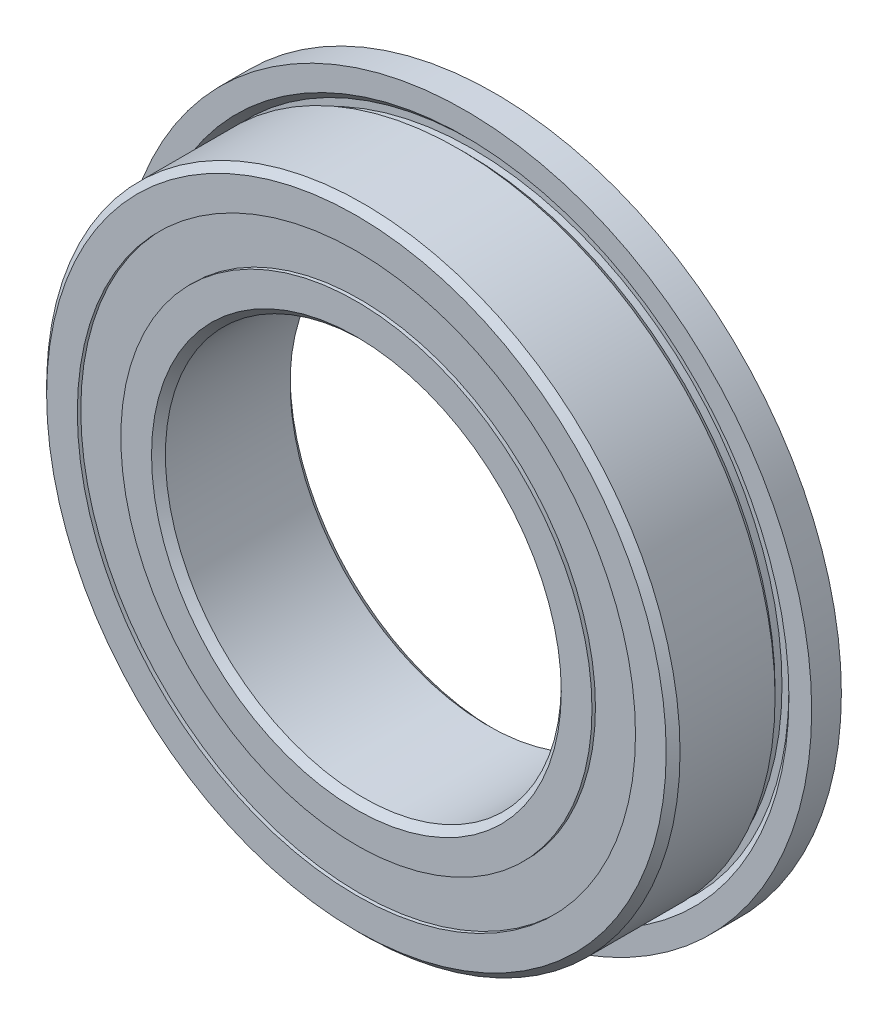
SolidWorks part; units mm, degrees
material "Alloy Steel"
ref_plane "Front Plane" through (0, 0, 0) normal (0, 0, 1) x (1, 0, 0)
ref_plane "Top Plane" through (0, 0, 0) normal (0, 1, 0) x (1, 0, 0)
ref_plane "Right Plane" through (0, 0, 0) normal (1, 0, 0) x (0, 0, -1)
sketch "Sketch1" plane through (0, 0, 0) normal (0, 0, 1) x (1, 0, 0)
  circle A0 centre (0, 0) radius 10
  dimension "ID" = 20
sketch "Sketch2" plane through (0, 0, 0) normal (1, 0, 0) x (0, 0, -1)
  line L0 (-3.5, 0) -> (3.5, 0) construction
  line L1 (0, 16) -> (0, -16) construction
  line L2 (3.15, 16) -> (-3.15, 16) construction
  line L3 (-3.15, 16) -> (-3.5, 15.65)
  line L4 (-3.5, 15.65) -> (-3.5, 14.0989)
  line L5 (-3.5, 14.0989) -> (-1.5556, 14.0989)
  line L6 (3.5, 14.0989) -> (1.5556, 14.0989)
  line L7 (3.5, 15.65) -> (3.5, 14.0989)
  line L8 (3.15, 16) -> (3.5, 15.65) construction
  line L9 (0, 16) -> (0, 13) construction
  line L10 (0, 13) -> (0, 10) construction
  line L11 (2, 0) -> (2, 16) construction
  line L12 (3.5, 15.65) -> (3.5, 17.5)
  line L13 (3.5, 17.5) -> (2, 17.5)
  line L14 (2, 17.5) -> (2, 16.35)
  line L15 (2, 16.35) -> (2.35, 16)
  line L16 (2.35, 16) -> (2.35, 15.65)
  line L17 (2.35, 15.65) -> (2, 15.65)
  line L18 (2, 15.65) -> (1.65, 16)
  line L19 (-3.15, 16) -> (1.65, 16)
  line L20 (3.5, 17.5) -> (3.5, -17.5) construction
  line L21 (2, 16) -> (2, 16.35) construction
  line L22 (2, 16) -> (1.65, 16) construction
  line L23 (0, 10) -> (0, -10) construction
  arc A0 (-1.5556, 14.0989) -> (1.5556, 14.0989) centre (0, 13) cw
  point P14 (0, 10)
  point P15 (2, 0)
  point P25 (3.5, 0)
  point P29 (-3.15, -16)
  dimension "D1" = 45
  dimension "D2" = 0.35
  dimension "D3" = 3.1111
  dimension "D4" = 1.0989
  dimension "Flange Thickness" = 1.5
  dimension "Flange OD" = 35
  dimension "Width" = 7
  dimension "OD" = 32
sketch "Sketch7" plane through (0, 0, 0) normal (1, 0, 0) x (0, 0, -1)
  line L13 (3.5, 17.5) -> (2, 17.5)
  line L14 (2, 17.5) -> (2, 16.35)
  line L15 (2, 16.35) -> (2.35, 16)
  line L16 (2.35, 16) -> (2.35, 15.65)
  line L17 (2.35, 15.65) -> (2, 15.65)
  line L18 (2, 15.65) -> (1.65, 16)
  line L19 (1.65, 16) -> (-3.15, 16)
  line L20 (-3.15, 16) -> (-3.5, 15.65)
  line L21 (-3.5, 15.65) -> (-3.5, 14.0989)
  line L22 (-3.5, 14.0989) -> (-1.5556, 14.0989)
  line L23 (1.5556, 14.0989) -> (3.5, 14.0989)
  line L24 (3.5, 14.0989) -> (3.5, 15.65)
  line L25 (3.5, 15.65) -> (3.5, 17.5)
  line L26 (3.5, 17.5) -> (2, 17.5)
  line L27 (2, 17.5) -> (2, 16.35)
  line L28 (2, 16.35) -> (2.35, 16)
  line L29 (2.35, 16) -> (2.35, 15.65)
  line L30 (2.35, 15.65) -> (2, 15.65)
  line L31 (2, 15.65) -> (1.65, 16)
  line L32 (1.65, 16) -> (-3.15, 16)
  line L33 (-3.15, 16) -> (-3.5, 15.65)
  line L34 (-3.5, 15.65) -> (-3.5, 14.0989)
  line L35 (-3.5, 14.0989) -> (-1.5556, 14.0989)
  line L36 (1.5556, 14.0989) -> (3.5, 14.0989)
  line L37 (3.5, 14.0989) -> (3.5, 15.65)
  line L38 (3.5, 15.65) -> (3.5, 17.5)
  arc A1 (1.5556, 14.0989) -> (-1.5556, 14.0989) centre (0, 13) ccw
  arc A2 (1.5556, 14.0989) -> (-1.5556, 14.0989) centre (0, 13) ccw
  dimension "D1" = 0
revolve "Revolve7" add sketch "Sketch7" angle 360 about L0
sketch "Sketch3" plane through (0, 0, 0) normal (1, 0, 0) x (0, 0, -1)
  line L0 (-3.5, 11.9011) -> (-1.5556, 11.9011)
  line L1 (0, 16) -> (0, -16) construction
  line L2 (-3.5, 15.65) -> (-3.5, 14.0989) construction
  line L3 (-3.5, 11.9011) -> (-3.5, 10.35)
  line L4 (-3.15, 16) -> (-3.5, 15.65) construction
  line L5 (-3.5, 10.35) -> (-3.15, 10)
  line L6 (-3.15, 10) -> (3.15, 10)
  line L8 (3.15, 10) -> (3.5, 10.35)
  line L10 (3.5, 10.35) -> (3.5, 11.9011)
  line L11 (3.5, 11.9011) -> (1.5556, 11.9011)
  line L13 (3.15, 16) -> (3.5, 15.65) construction
  arc A0 (1.5556, 14.0989) -> (-1.5556, 14.0989) centre (0, 13) ccw construction
  arc A1 (1.5556, 11.9011) -> (-1.5556, 11.9011) centre (0, 13) cw
revolve "Revolve3" add sketch "Sketch3" angle 360 about L0
sketch "Sketch6" plane through (0, 0, 0) normal (1, 0, 0) x (0, 0, -1)
  line L1 (-0.1832, 13.5495) -> (0.1832, 13.5495)
  line L2 (-0.1832, 13.5495) -> (-0.1832, 12.4505)
  line L3 (-0.1832, 12.4505) -> (0.1832, 12.4505)
  line L4 (0.1832, 13.5495) -> (0.1832, 12.4505)
  line L5 (-0.1832, 13.5495) -> (0.1832, 12.4505) construction
  line L6 (-0.1832, 12.4505) -> (0.1832, 13.5495) construction
  point P4 (0, 13)
  dimension "D1" = 1.0989
  dimension "D2" = 0.3663
revolve "Revolve6" add sketch "Sketch6" angle 360 about L0
sketch "Sketch4" plane through (0, 0, 0) normal (1, 0, 0) x (0, 0, -1)
  line L0 (-1.9046, 13) -> (1.9046, 13)
  arc A2 (-1.9046, 13) -> (1.9046, 13) centre (0, 13) cw
  arc A3 (1.5556, 14.0989) -> (-1.5556, 14.0989) centre (0, 13) ccw construction
revolve "Revolve4" add sketch "Sketch4" angle 360 about L0
ref_axis "Axis1" through (0, 0, -3.5) along (0, 0, 1)
pattern_circular "CirPattern1" count 13 over 360 about axis through (0, 0, -3.5) along (0, 0, 1) of bodies 104
sketch "Sketch5" plane through (0, 0, 0) normal (1, 0, 0) x (0, 0, -1)
  line L0 (-3.5, 14.0989) -> (-1.5556, 14.0989) construction
  line L1 (-3.325, 14.0989) -> (-1.9046, 14.0989)
  line L2 (-3.325, 14.0989) -> (-3.325, 11.9011)
  line L3 (-3.325, 11.9011) -> (-1.9046, 11.9011)
  line L4 (-1.9046, 14.0989) -> (-1.9046, 11.9011)
  line L5 (-3.5, 11.9011) -> (-1.5556, 11.9011) construction
  line L6 (3.5, 14.0989) -> (1.5556, 14.0989) construction
  line L7 (3.325, 14.0989) -> (1.9046, 14.0989)
  line L8 (3.325, 14.0989) -> (3.325, 11.9011)
  line L9 (3.325, 11.9011) -> (1.9046, 11.9011)
  line L10 (1.9046, 14.0989) -> (1.9046, 11.9011)
  line L11 (3.5, 11.9011) -> (1.5556, 11.9011) construction
  line L12 (-3.15, 16) -> (-3.5, 15.65) construction
  point P18 (-3.325, 15.825)
revolve "Revolve5" add sketch "Sketch5" angle 360 about L0
equation "\"D2@Sketch2\" = \"Width@Sketch2\" * .05"
equation "\"D3@Sketch2\" = \"Width@Sketch2\" / 2.25"
equation "\"D4@Sketch2\" =  (  (  ( \"OD@Sketch2\" - \"Width@Sketch2\" )  / 2 )  / 3.25 )  / 3.5"
equation "\"D2@CirPattern1\" = 360/\"Balls@CirPattern1\""
equation "\"D1@Sketch6\" = \"D4@Sketch2\""
equation "\"D2@Sketch6\"=\"D1@Sketch6\"/3"
